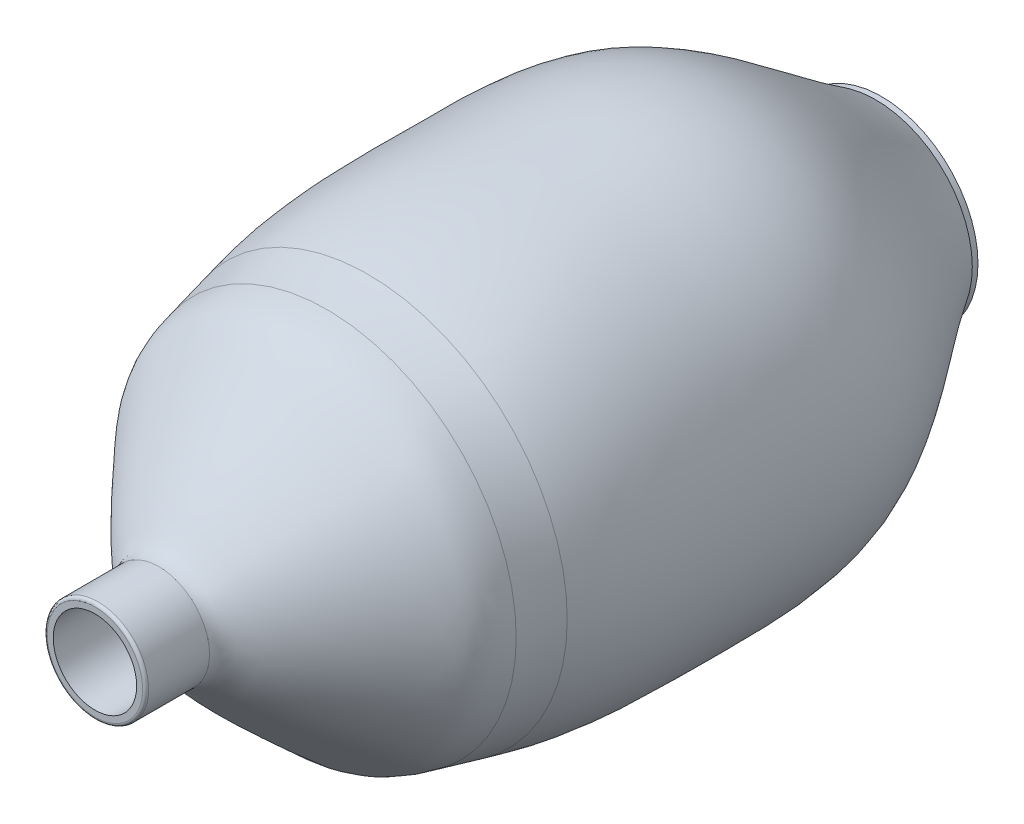
SolidWorks part; units mm, degrees
ref_plane "Front Plane" through (0, 0, 0) normal (0, 0, 1) x (1, 0, 0)
ref_plane "Top Plane" through (0, 0, 0) normal (0, 1, 0) x (1, 0, 0)
ref_plane "Right Plane" through (0, 0, 0) normal (1, 0, 0) x (0, 0, -1)
sketch "Sketch1" plane through (0, 0, 0) normal (1, 0, 0) x (0, 0, -1)
  line L0 (-102.2145, 99.2914) -> (313.4994, 99.2914) construction
  line L1 (397.8297, 442.0307) -> (397.8297, 437.4653)
  line L2 (400.8297, 443.7064) -> (402.7273, 443.7064)
  line L3 (293.3508, 411.4958) -> (293.3508, 478.9958) construction
  line L4 (150.9581, 411.4958) -> (150.9581, 428.4178) construction
  line L5 (140.2677, 425.4178) -> (140.2677, 428.4178)
  line L6 (140.2677, 428.4178) -> (161.5702, 428.4178)
  line L11 (143.2677, 425.4178) -> (161.7586, 425.4178)
  line L14 (143.2677, 414.4958) -> (397.8297, 414.4958) construction
  line L15 (150.9581, 411.4958) -> (252.6431, 411.4958) construction
  line L17 (140.2677, 411.4958) -> (400.8297, 411.4958) construction
  line L19 (143.2677, 425.4178) -> (140.2677, 425.4178)
  line L20 (140.2677, 411.4958) -> (140.2677, 428.4178) construction
  line L21 (143.2677, 414.4958) -> (143.2677, 425.4178) construction
  line L22 (402.7273, 443.7064) -> (402.7273, 437.4653)
  line L23 (402.7273, 437.4653) -> (397.8297, 437.4653)
  line L24 (400.8297, 443.7064) -> (400.8297, 411.4958) construction
  line L25 (397.8297, 442.0307) -> (397.8297, 414.4958) construction
  spline S0 degree 3 poles (161.5702, 428.4178) (165.3873, 428.899) (168.912, 433.839) (180.9569, 447.6583) (194.0295, 459.1878) (209.7892, 474.1296) (219.5746, 474.874) (225.7614, 476.3256) knots 0 0 0 0 0.122906 0.21711 0.671782 0.762907 1 1 1 1
  spline S1 degree 3 poles (225.7614, 476.3256) (250.0972, 483.9475) (288.2662, 483.1781) (352.9409, 484.0723) (383.1024, 454.4563) (400.8297, 443.7064) knots 0 0 0 0 0.382825 0.647952 1 1 1 1
  spline S2 degree 1 poles (161.7586, 425.4178) (226.5534, 473.43) knots 0 0 1 1 construction
  spline S3 degree 1 poles (226.5534, 473.43) (397.8297, 442.0307) knots 0 0 1 1 construction
  spline S4 degree 3 poles (161.7586, 425.4178) (161.8194, 425.4255) (161.9231, 425.4381) (162.2747, 425.4851) (162.8182, 425.5779) (163.9129, 425.8344) (165.9085, 426.5942) (168.2182, 428.2193) (170.2534, 430.4407) (171.8734, 432.5301) (173.4434, 434.4347) (175.6344, 436.9712) (178.4641, 440.064) (181.968, 443.6977) (185.5643, 447.264) (189.2372, 450.7867) (192.9708, 454.2863) (196.7484, 457.7831) (199.92, 460.716) (202.4615, 463.0766) (204.3718, 464.8767) (206.1934, 466.5371) (207.9885, 467.9617) (209.7846, 469.0616) (211.8124, 469.9787) (214.014, 470.7294) (217.1535, 471.5593) (221.3562, 472.3649) (224.8419, 473.0284) (226.5534, 473.43) knots -0.002006 -0.002006 -0.002006 -0.002006 -0.000046 0.001914 0.005833 0.013672 0.02935 0.060705 0.09206 0.123416 0.154771 0.186126 0.248837 0.311547 0.374258 0.436968 0.499679 0.562389 0.6251 0.656455 0.687811 0.719166 0.750521 0.781876 0.813232 0.844587 0.875942 0.938653 1.001363 1.001363 1.001363 1.001363
  spline S5 degree 3 poles (226.5534, 473.43) (227.5113, 473.73) (229.4424, 474.3136) (233.257, 475.3705) (237.9994, 476.5183) (243.6423, 477.6374) (251.1247, 478.8233) (260.426, 479.7961) (271.5954, 480.3565) (282.8538, 480.5238) (294.2873, 480.4961) (305.9479, 480.5443) (317.5275, 480.3297) (328.8608, 479.3923) (339.7598, 477.3486) (350.0061, 473.7229) (359.898, 468.4704) (369.5165, 462.1622) (378.962, 455.2772) (386.7753, 449.4977) (393.0722, 445.0991) (396.2246, 443.034) (397.8297, 442.0307) knots -0.000549 -0.000549 -0.000549 -0.000549 0.014939 0.030427 0.061402 0.092377 0.123352 0.185303 0.247254 0.309204 0.371155 0.433105 0.495056 0.557006 0.618957 0.680907 0.742858 0.804808 0.866759 0.928709 0.959685 0.99066 0.99066 0.99066 0.99066
  dimension "D1" = 3
  dimension "D2" = 67.5
revolve "Revolve1" add sketch "Sketch1" angle 360 about L15
fillet "Fillet1" radius 1 1 edges at (16.9221, 411.4958, -140.2677)
fillet "Fillet2" radius 261 1 edges at (64.8299, 411.4958, -225.7614)
